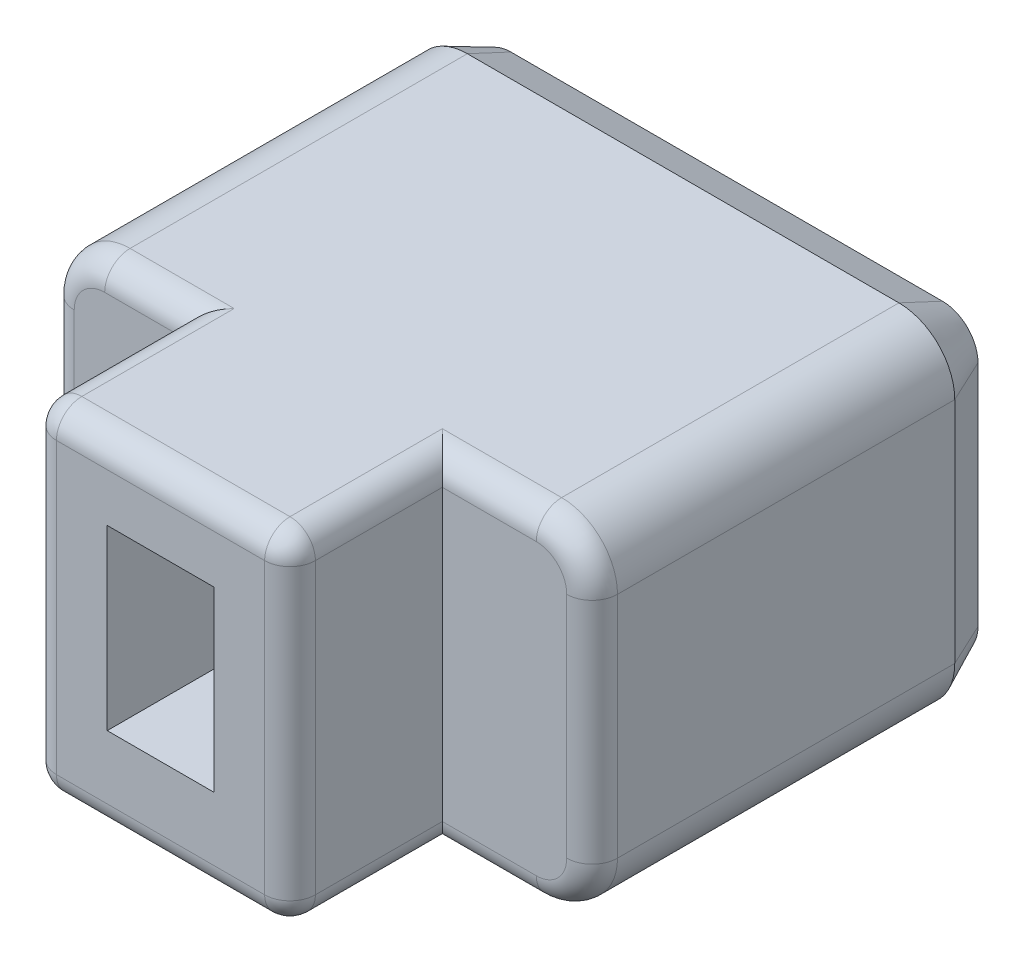
SolidWorks part; units mm, degrees
ref_plane "Plan de face" through (0, 0, 0) normal (0, 0, 1) x (1, 0, 0)
ref_plane "Plan de dessus" through (0, 0, 0) normal (0, 1, 0) x (1, 0, 0)
ref_plane "Plan de droite" through (0, 0, 0) normal (1, 0, 0) x (0, 0, -1)
sketch "Esquisse2" plane through (0, 0, 0) normal (0, 0, 1) x (1, 0, 0)
  line L1 (1.1, 0) -> (9.6, 0)
  line L2 (0, 1.1) -> (0, 5.6)
  line L3 (1.1, 6.7) -> (9.6, 6.7)
  line L4 (10.7, 1.1) -> (10.7, 5.6)
  arc A0 (9.6, 6.7) -> (10.7, 5.6) centre (9.6, 5.6) cw
  arc A1 (9.6, 0) -> (10.7, 1.1) centre (9.6, 1.1) ccw
  arc A2 (1.1, 0) -> (0, 1.1) centre (1.1, 1.1) cw
  arc A3 (0, 5.6) -> (1.1, 6.7) centre (1.1, 5.6) cw
  point P7 (10.7, 6.7)
  point P12 (0, 0)
  point P15 (0, 6.7)
  dimension "D3" = 1.1
  dimension "D1" = 10.7
  dimension "D2" = 6.7
extrude "Boss.-Extru.1" add sketch "Esquisse2" along normal blind 11
sketch "Esquisse3" plane through (0, 0, 11) normal (0, 0, 1) x (1, 0, 0)
  line L0 (0, 5.6) -> (0, 1.1) construction
  line L1 (4.15, 5.25) -> (6.25, 5.25)
  line L2 (4.15, 5.25) -> (4.15, 1.75)
  line L3 (4.15, 1.75) -> (6.25, 1.75)
  line L4 (6.25, 5.25) -> (6.25, 1.75)
  line L5 (10.7, 1.1) -> (10.7, 5.6) construction
  line L6 (9.6, 6.7) -> (1.1, 6.7) construction
  line L7 (1.1, 0) -> (9.6, 0) construction
  dimension "D1" = 2.1
  dimension "D2" = 3.5
  dimension "D3" = 4.15
  dimension "D4" = 4.45
  dimension "D5" = 1.45
  dimension "D6" = 1.75
extrude "Enlèv. mat.-Extru.1" cut sketch "Esquisse3" against normal blind 3
sketch "Esquisse4" plane through (0, 0, 11) normal (0, 0, 1) x (1, 0, 0)
  line L0 (2.65, 6.7) -> (2.65, 0)
  line L1 (9.6, 6.7) -> (1.1, 6.7) construction
  line L2 (1.1, 0) -> (9.6, 0) construction
  line L3 (2.65, 0) -> (7.75, 0)
  line L4 (7.75, 0) -> (7.75, 6.7)
  line L5 (7.75, 6.7) -> (2.65, 6.7)
  line L6 (4.15, 5.25) -> (4.15, 1.75) construction
  line L7 (6.25, 1.75) -> (6.25, 5.25) construction
  dimension "D1" = 1.5
  dimension "D2" = 1.5
extrude "Enlèv. mat.-Extru.2" cut sketch "Esquisse4" against normal blind 3 flip side to cut
fillet "Congé1" radius 0.5 18 edges at (8.675, 0, 8) (10.3778, 0.3222, 8) (10.7, 3.35, 8) (10.3778, 6.3778, 8) (1.875, 6.7, 8) (0.3222, 6.3778, 8) (1.875, 0, 8) (0.3222, 0.3222, 8) (7.75, 6.7, 9.5) (2.65, 6.7, 9.5) (7.75, 0, 9.5) (2.65, 0, 9.5) (2.65, 3.35, 11) (5.2, 6.7, 11) (7.75, 3.35, 11) (5.2, 0, 11) (8.675, 6.7, 8) (0, 3.35, 8)
chamfer "Chanfrein1" distance 0.4 angle 65 8 edges at (5.35, 0, 0) (10.3778, 0.3222, 0) (0.3222, 0.3222, 0) (10.7, 3.35, 0) (0, 3.35, 0) (10.3778, 6.3778, 0) (0.3222, 6.3778, 0) (5.35, 6.7, 0) first distance on face at (5.35, 3.35, 0)
